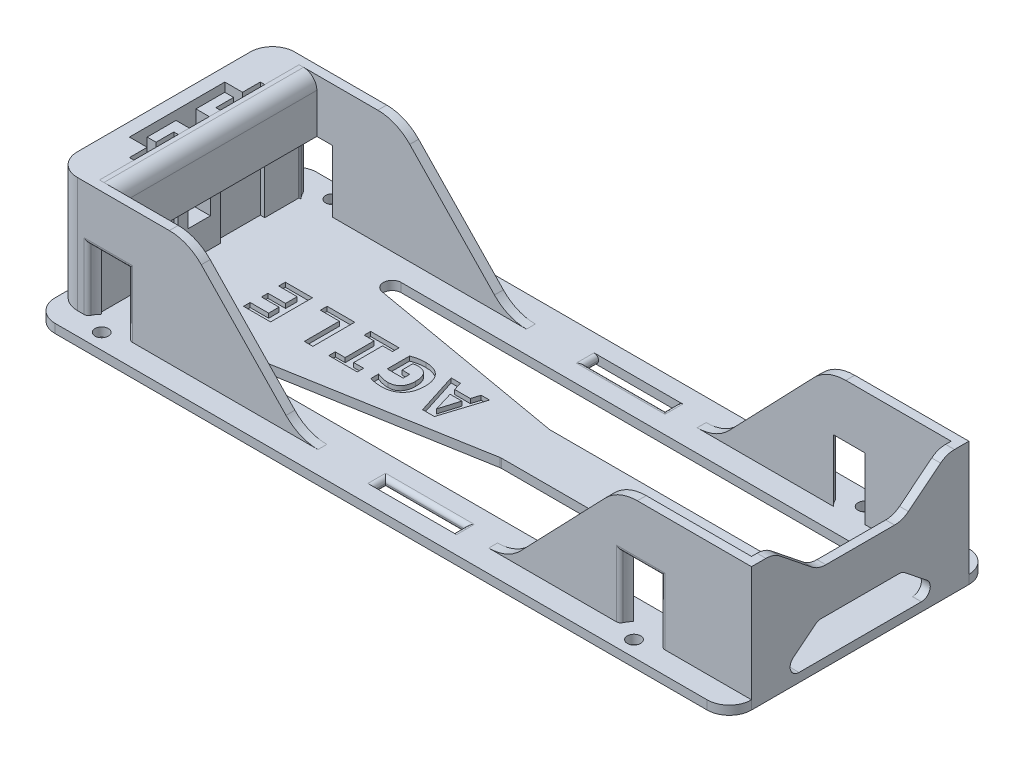
SolidWorks part; units mm, degrees
ref_plane "Спереди" through (0, 0, 0) normal (0, 0, 1) x (1, 0, 0)
ref_plane "Сверху" through (0, 0, 0) normal (0, 1, 0) x (1, 0, 0)
ref_plane "Справа" through (0, 0, 0) normal (1, 0, 0) x (0, 0, -1)
sketch "Эскиз1" plane through (0, 0, 0) normal (0, 1, 0) x (1, 0, 0)
  line L0 (-78.6693, 22.7404) -> (-78.6693, 24.7404) construction
  line L1 (-78.6693, 22.7404) -> (68.3307, 22.7404)
  line L2 (-78.6693, 22.7404) -> (-78.6693, -22.2596)
  line L3 (-78.6693, -22.2596) -> (68.3307, -22.2596)
  line L4 (68.3307, 22.7404) -> (68.3307, -22.2596)
  line L5 (-78.6693, 24.7404) -> (68.3307, 24.7404) construction
  line L6 (68.3307, 24.7404) -> (70.3307, 24.7404) construction
  line L7 (70.3307, 24.7404) -> (70.3307, -22.2596) construction
  line L8 (70.3307, -22.2596) -> (70.3307, -24.2596) construction
  line L9 (70.3307, -24.2596) -> (-78.6693, -24.2596) construction
  line L10 (-78.6693, -24.2596) -> (-78.6693, -22.2596) construction
  line L11 (-78.6693, 22.7404) -> (-86.6693, 22.7404) construction
  line L12 (-86.6693, 22.7404) -> (-86.6693, -22.2596) construction
  line L13 (-86.6693, -22.2596) -> (-78.6693, -22.2596) construction
  line L14 (70.3307, 24.7404) -> (70.3307, -24.2596)
  line L15 (70.3307, -24.2596) -> (-86.6693, -24.2596)
  line L16 (-86.6693, -24.2596) -> (-86.6693, 24.7404)
  line L17 (-86.6693, 24.7404) -> (70.3307, 24.7404)
extrude "Бобышка-Вытянуть1" add sketch "Эскиз1" along normal blind 26
sketch "Эскиз2" plane through (0, 0, 0) normal (0, -1, 0) x (1, 0, 0)
  line L1 (-86.6693, -24.7404) -> (70.3307, -24.7404)
  line L2 (-86.6693, -24.7404) -> (-86.6693, 24.2596)
  line L3 (-86.6693, 24.2596) -> (70.3307, 24.2596)
  line L4 (70.3307, -24.7404) -> (70.3307, 24.2596)
extrude "Бобышка-Вытянуть2" add sketch "Эскиз2" along normal blind 2
sketch "Эскиз4" plane through (0, 26, 0) normal (0, 1, 0) x (1, 0, 0)
  line L0 (-78.6693, -22.2596) -> (-78.6693, 22.7404) construction
  line L1 (-78.6693, -9.5096) -> (-78.6693, 9.9904) construction
  line L2 (-78.6693, -4.5096) -> (-78.6693, -14.5096)
  line L3 (-78.6693, 4.9904) -> (-78.6693, 14.9904)
  line L4 (-78.6693, -14.5096) -> (-79.6693, -14.5096)
  line L5 (-78.6693, -4.5096) -> (-79.6693, -4.5096)
  line L6 (-79.6693, -14.5096) -> (-79.6693, -10.5096)
  line L7 (-78.6693, 14.9904) -> (-79.6693, 14.9904)
  line L8 (-78.6693, 4.9904) -> (-79.6693, 4.9904)
  line L9 (-79.6693, -4.5096) -> (-79.6693, -8.5096)
  line L10 (-79.6693, 4.9904) -> (-79.6693, 8.9904)
  line L11 (-79.6693, 14.9904) -> (-79.6693, 10.9904)
  line L12 (-79.6693, 10.9904) -> (-83.6693, 10.9904)
  line L13 (-83.6693, 10.9904) -> (-83.6693, -10.5096)
  line L14 (-83.6693, -10.5096) -> (-79.6693, -10.5096)
  line L15 (-79.6693, -8.5096) -> (-81.6693, -8.5096)
  line L17 (-81.6693, 8.9904) -> (-79.6693, 8.9904)
  line L18 (-78.6693, 0.2404) -> (-78.6693, -2.0096)
  line L19 (-78.6693, -2.0096) -> (-81.6693, -2.0096)
  line L20 (-81.6693, -2.0096) -> (-81.6693, -8.5096)
  line L21 (-78.6693, 0.2404) -> (-78.6693, 2.4904)
  line L22 (-78.6693, 2.4904) -> (-81.6693, 2.4904)
  line L24 (-81.6693, 2.4904) -> (-81.6693, 8.9904)
  point P7 (-78.6693, 0.2404)
  point P9 (-78.6693, -9.5096)
  point P13 (-78.6693, 9.9904)
extrude "Вырез-Вытянуть1" cut sketch "Эскиз4" against normal blind 10
sketch "Эскиз5" plane through (0, 16, 0) normal (0, 1, 0) x (1, 0, 0)
  line L1 (-78.6693, -14.5096) -> (-79.6693, -14.5096)
  line L2 (-78.6693, -14.5096) -> (-78.6693, -4.5096)
  line L3 (-78.6693, -4.5096) -> (-79.6693, -4.5096)
  line L4 (-79.6693, -14.5096) -> (-79.6693, -4.5096)
  line L5 (-79.6693, 14.9904) -> (-78.6693, 14.9904)
  line L6 (-79.6693, 14.9904) -> (-79.6693, 4.9904)
  line L7 (-79.6693, 4.9904) -> (-78.6693, 4.9904)
  line L8 (-78.6693, 14.9904) -> (-78.6693, 4.9904)
extrude "Вырез-Вытянуть2" cut sketch "Эскиз5" against normal blind 16
sketch "Эскиз6" plane through (-86.6693, 0, 0) normal (-1, 0, 0) x (0, 0, 1)
  line L0 (24.2596, -2) -> (-24.7404, -2) construction
  line L1 (-0.2404, -2) -> (-0.2404, 12) construction
  line L2 (2.2596, 12) -> (-2.7404, 12) construction
  line L3 (2.2596, 17.5) -> (2.2596, 6.5) construction
  line L4 (2.2596, 6.5) -> (-2.7404, 6.5) construction
  line L5 (-2.7404, 6.5) -> (-2.7404, 17.5) construction
  line L6 (-2.7404, 17.5) -> (2.2596, 17.5) construction
  line L7 (-2.7404, 17.5) -> (-2.7404, 6.5)
  line L8 (-2.7404, 6.5) -> (2.2596, 6.5)
  line L9 (2.2596, 6.5) -> (2.2596, 17.5)
  line L10 (2.2596, 17.5) -> (-2.7404, 17.5)
  point P9 (-0.2404, 12)
  point P12 (2.2596, 12)
extrude "Вырез-Вытянуть3" cut sketch "Эскиз6" against normal blind 8
sketch "Эскиз7" plane through (0, -2, 0) normal (0, -1, 0) x (1, 0, 0)
  line L0 (70.3307, -24.7404) -> (70.3307, -29.7404)
  line L1 (-86.6693, 29.2596) -> (70.3307, 29.2596)
  line L5 (-86.6693, -24.7404) -> (-86.6693, -29.7404)
  line L6 (-86.6693, 24.2596) -> (70.3307, 24.2596)
  line L7 (-74.6693, -26.2404) -> (-86.6693, -26.2404) construction
  line L8 (-74.6693, 25.7596) -> (-86.6693, 25.7596) construction
  line L9 (70.3307, -24.7404) -> (-86.6693, -24.7404)
  line L10 (70.3307, -26.2404) -> (45.3307, -26.2404) construction
  line L11 (45.3307, -26.2404) -> (45.3307, 25.7596) construction
  line L14 (-86.6693, 24.2596) -> (-86.6693, 29.2596)
  line L21 (70.3307, 24.2596) -> (70.3307, 29.2596)
  line L22 (-86.6693, -29.7404) -> (70.3307, -29.7404)
  circle A0 centre (45.3307, -26.2404) radius 1.5
  circle A1 centre (-74.6693, -26.2404) radius 1.5
  circle A2 centre (-74.6693, 25.7596) radius 1.5
  circle A3 centre (45.3307, 25.7596) radius 1.5
  point P9 (-86.6693, -6.3534)
  line M7 (-86.6693, 24.2596) -> (-86.6693, -24.7404)
  line M8 (-86.6693, -24.7404) -> (70.3307, -24.7404)
  line M9 (70.3307, -24.7404) -> (70.3307, 24.2596)
  line M10 (70.3307, 24.2596) -> (-86.6693, 24.2596)
extrude "Бобышка-Вытянуть5" add sketch "Эскиз7" against normal blind 2 contours L6 A3 L21 L1 L14 A2 M10 | L9 A1 L5 L22 L0 A0 M8 | L6 L9 M10 M7 M8 M9 region at (-8.0501, -2, -27.2588) region at (-8.1693, -2, -0.2404) region at (-8.0501, -2, 26.7779)
ref_plane "Плоскость1" through (-78.6693, 26, 4.5096) normal (0, 1, 0) x (1, 0, 0)
sketch "Эскиз16" plane through (0, 26, 0) normal (0, 1, 0) x (1, 0, 0)
  line L0 (68.3307, 22.7404) -> (-78.6693, 22.7404) construction
  line L1 (-78.6693, -22.2596) -> (-74.6693, -22.2596)
  line L3 (-78.6693, 22.7404) -> (-74.6693, 22.7404)
  line L4 (-74.6693, -22.2596) -> (-74.6693, 22.7404)
  line L5 (-78.6693, -22.2596) -> (-78.6693, -14.5096)
  line L9 (-78.6693, -2.0096) -> (-78.6693, -4.5096) construction
  line L10 (-78.6693, -4.5096) -> (-78.6693, -2.0096)
  line L11 (-81.6693, -2.0096) -> (-78.6693, -2.0096) construction
  line L12 (-78.6693, -2.0096) -> (-78.6693, 2.4904)
  line L13 (-78.6693, 2.4904) -> (-78.6693, 4.9904)
  line L17 (-78.6693, 14.9904) -> (-78.6693, 22.7404)
  line L18 (-78.6693, 4.9904) -> (-78.6693, 14.9904)
  line L19 (-78.6693, -14.5096) -> (-78.6693, -4.5096)
extrude "Бобышка-Вытянуть9" add sketch "Эскиз16" against normal blind 12 separate body
sketch "Эскиз8" plane through (0, 0, 0) normal (0, 1, 0) x (1, 0, 0)
  circle A0 centre (45.3307, 26.2404) radius 5
  circle A1 centre (-74.6693, 26.2404) radius 5
  circle A2 centre (-74.6693, -25.7596) radius 5
  circle A3 centre (45.3307, -25.7596) radius 5
extrude "Вырез-Вытянуть4" cut sketch "Эскиз8" along normal blind 14
sketch "Эскиз17" plane through (0, 0, -24.7404) normal (0, 0, -1) x (-1, 0, 0)
  line L0 (-70.3307, 26) -> (-40.3307, 26) construction
  line L1 (-70.3307, 26) -> (86.6693, 26) construction
  line L2 (86.6693, 26) -> (56.6693, 26) construction
  line L3 (-70.3307, 0) -> (-15.3307, 0) construction
  line L4 (69.8996, 0) -> (-40.561, 0) construction
  line L5 (86.6693, 0) -> (31.6693, 0) construction
  line L6 (-40.3307, 26) -> (-15.3307, 0)
  line L7 (-15.3307, 0) -> (31.6693, 0)
  line L8 (31.6693, 0) -> (56.6693, 26)
  line L9 (56.6693, 26) -> (-40.3307, 26)
extrude "Вырез-Вытянуть5" cut sketch "Эскиз17" against normal blind 49
fillet "Скругление5" radius 10 8 edges at (40.3307, 26, 23.2596) (15.3307, 0, 23.2596) (15.3307, 0, -23.7404) (40.3307, 26, -23.7404) (-31.6693, 0, 23.2596) (-31.6693, 0, -23.7404) (-56.6693, 26, 23.2596) (-56.6693, 26, -23.7404)
fillet "Скругление6" radius 5 2 edges at (-86.6693, 13, -24.7404) (-86.6693, 13, 24.2596)
fillet "Скругление7" radius 5 4 edges at (-86.6693, -1, 29.2596) (-86.6693, -1, -29.7404) (70.3307, -1, -29.7404) (70.3307, -1, 29.2596)
sketch "Эскиз19" plane through (70.3307, 0, 0) normal (1, 0, 0) x (0, 0, -1)
  line L0 (-24.2596, 26) -> (-19.2596, 26) construction
  line L1 (-24.2596, 26) -> (24.7404, 26) construction
  line L2 (24.7404, 26) -> (19.7404, 26) construction
  line L3 (-24.2596, 0) -> (24.7404, 0) construction
  line L4 (24.7404, 0) -> (24.7404, 10) construction
  line L5 (24.7404, 26) -> (24.7404, 0) construction
  line L6 (19.7404, 18) -> (9.7404, 18) construction
  line L7 (19.7404, 8) -> (-9.2596, 8) construction
  line L8 (-19.2596, 26) -> (-19.2596, 18) construction
  line L9 (19.7404, 26) -> (19.7404, 18) construction
  line L10 (-19.2596, 18) -> (-9.2596, 18) construction
  line L11 (-19.2596, 26) -> (19.7404, 26)
  line L12 (19.7404, 26) -> (9.7404, 18)
  line L13 (9.7404, 18) -> (-9.2596, 18)
  line L14 (-9.2596, 18) -> (-19.2596, 26)
  line L15 (-19.2596, 0) -> (-19.2596, 6) construction
  line L16 (19.7404, 0) -> (19.7404, 8) construction
  line L17 (-19.2596, 0) -> (19.7404, 0)
  line L20 (-9.2596, 8) -> (-19.2596, 0)
  line L21 (19.7404, 0) -> (9.7404, 8)
  line L22 (9.7404, 8) -> (-9.2596, 8)
extrude "Вырез-Вытянуть6" cut sketch "Эскиз19" against normal blind 2
fillet "Скругление8" radius 5 4 edges at (69.3307, 18, -9.7404) (69.3307, 26, -19.7404) (69.3307, 18, 9.2596) (69.3307, 26, 19.2596)
fillet "Скругление10" radius 1 4 edges at (-74.6693, 14, 24.2596) (45.3307, 14, 24.2596) (45.3307, 14, -24.7404) (-74.6693, 14, -24.7404)
fillet "Скругление11" radius 1 8 edges at (50.1004, 7.5, -24.7404) (40.561, 7.5, -24.7404) (-79.439, 7.5, -24.7404) (-69.8996, 7.5, -24.7404) (-79.439, 7.5, 24.2596) (-69.8996, 7.5, 24.2596) (40.561, 7.5, 24.2596) (50.1004, 7.5, 24.2596)
sketch "Эскиз20" plane through (0, 0, 0) normal (0, 1, 0) x (1, 0, 0)
  line L0 (-78.6693, 22.7404) -> (68.3307, 22.7404) construction
  line L1 (-14.1693, 22.7404) -> (3.8307, 22.7404)
  line L2 (3.8307, 22.7404) -> (3.8307, 25.7404)
  line L3 (3.8307, 25.7404) -> (-14.1693, 25.7404)
  line L4 (-14.1693, 25.7404) -> (-14.1693, 22.7404)
  line L5 (-78.6693, -22.2596) -> (68.3307, -22.2596) construction
  line L6 (-14.1693, -22.2596) -> (3.8307, -22.2596)
  line L7 (-14.1693, -22.2596) -> (-14.1693, -25.2596)
  line L8 (-14.1693, -25.2596) -> (3.8307, -25.2596)
  line L9 (3.8307, -25.2596) -> (3.8307, -22.2596)
  point P7 (-5.1693, 22.7404)
  point P16 (-5.1693, -22.2596)
extrude "Вырез-Вытянуть8" cut sketch "Эскиз20" against normal blind 2
fillet "Скругление13" radius 3 1 edges at (-74.6693, 26, -0.2404)
fillet "Скругление14" radius 1 12 edges at (3.8307, 0, -24.2404) (-14.1693, 0, -24.2404) (-5.1693, 0, -22.7404) (3.8307, 0, 23.7596) (-14.1693, 0, 23.7596) (-5.1693, 0, 22.2596) (-5.1693, -2, 22.2596) (3.8307, -2, 23.7596) (-14.1693, -2, 23.7596) (3.8307, -2, -24.2404) (-5.1693, -2, -22.7404) (-14.1693, -2, -24.2404)
sketch "Эскиз21" plane through (0, 0, 0) normal (0, 1, 0) x (1, 0, 0)
  line L0 (68.3307, -22.2596) -> (68.3307, -17.2596) construction
  line L1 (68.3307, -22.2596) -> (68.3307, -19.2596) construction
  line L2 (68.3307, -17.2596) -> (-78.6693, -17.2596) construction
  line L3 (-78.6693, -14.5096) -> (-78.6693, -22.2596) construction
  line L4 (68.3307, 22.7404) -> (68.3307, 17.7404) construction
  line L5 (68.3307, 17.7404) -> (-78.6693, 17.7404) construction
  line L6 (-78.6693, 22.7404) -> (-78.6693, 14.9904) construction
  line L7 (-5.1693, 17.7404) -> (-5.1693, 5.7404) construction
  line L8 (-5.1693, -17.2596) -> (-5.1693, -5.2596) construction
  line L9 (68.3307, 17.7404) -> (48.3307, 17.7404) construction
  line L10 (48.3307, 17.7404) -> (48.3307, 5.7404) construction
  line L11 (48.3307, 5.7404) -> (-5.1693, 5.7404) construction
  line L12 (48.3307, -17.2596) -> (48.3307, -5.2596) construction
  line L13 (48.3307, -5.2596) -> (-5.1693, -5.2596) construction
  line L15 (48.3307, 5.7404) -> (-5.1693, 5.7404)
  line L19 (48.3307, -5.2596) -> (-5.1693, -5.2596)
  line L22 (68.3307, 17.7404) -> (63.3307, 17.7404) construction
  line L23 (63.3307, 17.7404) -> (63.3307, 14.7404) construction
  line L27 (63.3307, 17.7404) -> (48.3307, 5.7404)
  line L28 (68.3307, -17.2596) -> (63.3307, -17.2596) construction
  line L29 (48.3307, -5.2596) -> (63.3307, -17.2596)
  line L31 (-78.6693, 17.7404) -> (-73.6693, 17.7404) construction
  line L32 (-78.6693, -17.2596) -> (-73.6693, -17.2596) construction
  line L33 (-5.1693, -5.2596) -> (-73.6693, -17.2596)
  line L34 (-73.6693, -17.2596) -> (63.3307, -17.2596)
  line L35 (-5.1693, 5.7404) -> (-73.6693, 17.7404)
  line L36 (-73.6693, 17.7404) -> (63.3307, 17.7404)
extrude "Вырез-Вытянуть9" cut sketch "Эскиз21" against normal blind 2
fillet "Скругление16" radius 2 8 edges at (-5.1693, -1, 5.2596) (-5.1693, -1, -5.7404) (48.3307, -1, 5.2596) (48.3307, -1, -5.7404) (63.3307, -1, -17.7404) (63.3307, -1, 17.2596) (-73.6693, -1, -17.7404) (-73.6693, -1, 17.2596)
sketch "Эскиз22" plane through (0, 0, 0) normal (0, 1, 0) x (1, 0, 0)
  line L0 (-4.9955, -5.2596) -> (-69.621, -5.2596) construction
  line L1 (-4.9955, 4.7404) -> (-64.9955, 4.7404) construction
  line L2 (-4.9955, 4.7404) -> (-4.9955, 5.7404) construction
  line L3 (-4.9955, 5.7404) -> (47.6291, 5.7404) construction
  text T0 "AGILE" font "Consolas" height in points 36
extrude "Вырез-Вытянуть10" cut sketch "Эскиз22" against normal blind 1
ref_plane "Плоскость2" through (-74.6693, 23, -22.7404) normal (0, 0, 1) x (1, 0, 0)
fillet "Скругление18" radius 2 4 edges at (69.3307, 0, -19.7404) (69.3307, 8, -9.7404) (69.3307, 8, 9.2596) (69.3307, 0, 19.2596)
